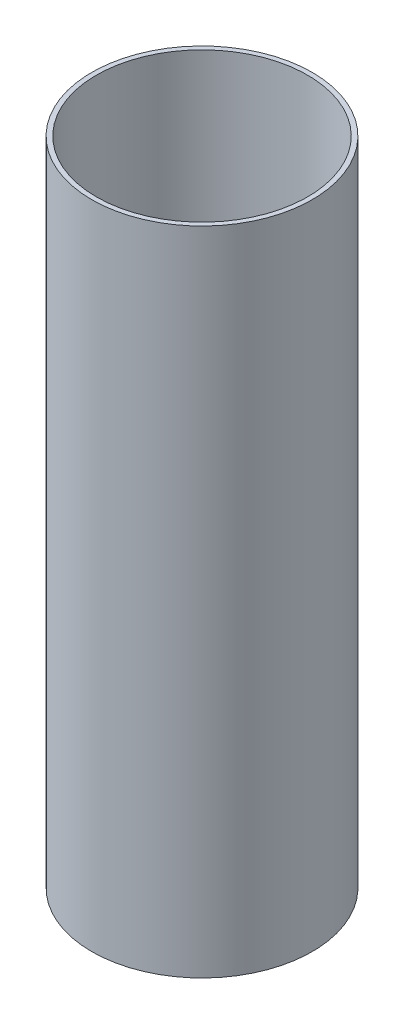
SolidWorks part; units mm, degrees
material "6063-T6"
ref_plane "Front Plane" through (0, 0, 0) normal (0, 0, 1) x (1, 0, 0)
ref_plane "Top Plane" through (0, 0, 0) normal (0, 1, 0) x (1, 0, 0)
ref_plane "Right Plane" through (0, 0, 0) normal (1, 0, 0) x (0, 0, -1)
sketch "Sketch1" plane through (0, 0, 0) normal (0, 1, 0) x (1, 0, 0)
  circle A0 centre (0, 0) radius 36.47
  circle A1 centre (0, 0) radius 38.1
  dimension "D1" = 72.94
  dimension "D2" = 1.63
extrude "Boss-Extrude1" add sketch "Sketch1" along normal blind 225
